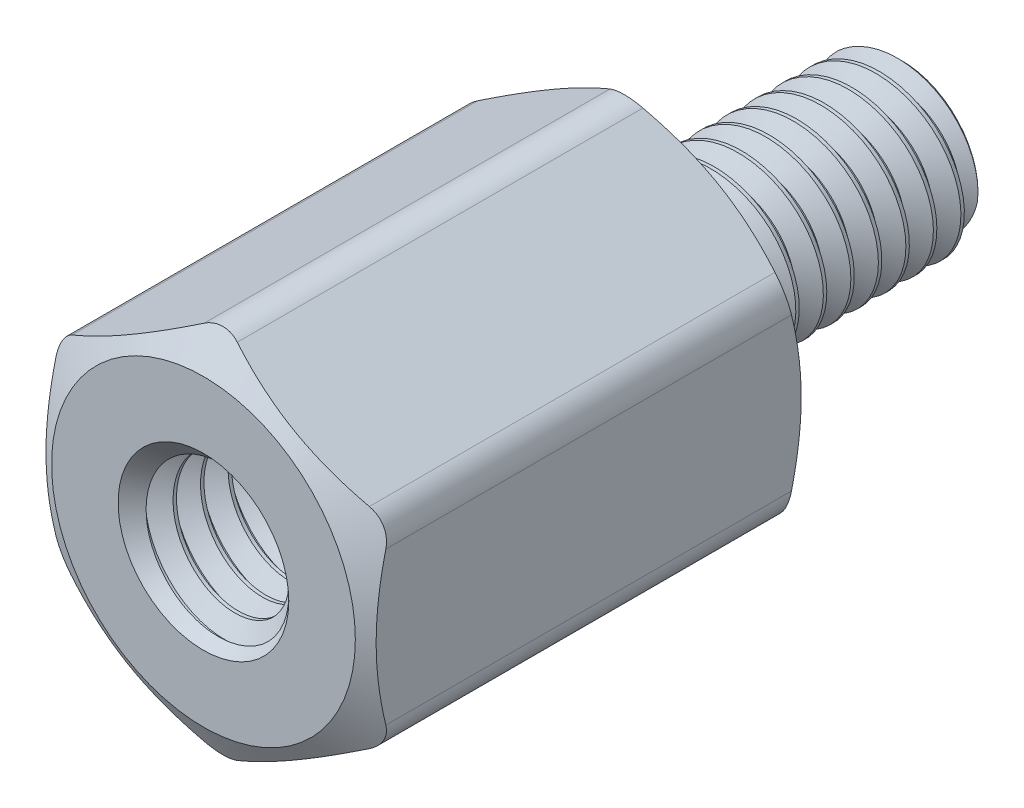
SolidWorks part; units mm, degrees
material "Nylon 6/10"
ref_plane "Front Plane" through (0, 0, 0) normal (0, 0, 1) x (1, 0, 0)
ref_plane "Top Plane" through (0, 0, 0) normal (0, 1, 0) x (1, 0, 0)
ref_plane "Right Plane" through (0, 0, 0) normal (1, 0, 0) x (0, 0, -1)
sketch "Sketch1" plane through (0, 0, 0) normal (0, 0, 1) x (1, 0, 0)
  line L1 (3, 1.7321) -> (0, 3.4641)
  line L2 (0, 3.4641) -> (-3, 1.7321)
  line L3 (-3, 1.7321) -> (-3, -1.7321)
  line L4 (-3, -1.7321) -> (0, -3.4641)
  line L5 (0, -3.4641) -> (3, -1.7321)
  line L6 (3, -1.7321) -> (3, 1.7321)
  circle A0 centre (0, 0) radius 3 construction
  point P10 (0, -3)
  dimension "Hex Size" = 6
sketch "Sketch2" plane through (0, 0, 0) normal (1, 0, 0) x (0, 0, -1)
  line L0 (4.7, 0) -> (-8, 0) construction
  line L2 (0, 1.5) -> (0, -1.5) construction
  line L3 (-3.2, 1.5) -> (-3.2, -1.5) construction
  line L4 (-8.4688, 1.5541) -> (-8.2188, 1.1211) construction
  line L5 (-8.2188, 1.1211) -> (-7.9688, 1.5541) construction
  line L6 (-7.9688, 1.5541) -> (-8.4688, 1.5541) construction
  line L7 (-8.4375, 1.5) -> (-8, 1.5) construction
  line L8 (-8.25, 1.1752) -> (-8.1875, 1.1752) construction
  line L9 (-8.2188, 1.1752) -> (-8.2188, 1.1211) construction
  line L10 (-8.2188, 1.5) -> (-8.2188, 1.5541) construction
  line L11 (4.6688, 1.5541) -> (5.1688, 1.5541) construction
  line L12 (5.1688, 1.5541) -> (4.9188, 1.1211) construction
  line L13 (4.9188, 1.1211) -> (4.6688, 1.5541) construction
  line L14 (4.7, 1.5) -> (5.1375, 1.5) construction
  line L15 (4.8875, 1.1752) -> (4.95, 1.1752) construction
  line L16 (4.9188, 1.1752) -> (4.9188, 1.1211) construction
  line L17 (4.9188, 1.5) -> (4.9188, 1.5541) construction
  line L18 (0, 3.4641) -> (-8, 3.4641) construction
  point P6 (0, 0)
  point P9 (-3.2, 0)
  dimension "Length" = 8
sketch "Sketch3" plane through (0, 0, 0) normal (1, 0, 0) x (0, 0, -1)
  line L0 (-3.2, 0) -> (4.7, 0)
  line L1 (-3.2, 1.5) -> (-3.2, -1.5) construction
  line L2 (4.7, 0) -> (4.7, 1.375)
  line L3 (4.7, 1.375) -> (4.575, 1.5)
  line L4 (4.575, 1.5) -> (0.7515, 1.5)
  line L5 (0.7515, 1.5) -> (0.564, 1.1752)
  line L6 (-3.2, 0) -> (-3.2, 1.375)
  line L7 (-3.2, 1.375) -> (-3.325, 1.5)
  line L8 (-3.325, 1.5) -> (-7.875, 1.5)
  line L9 (-7.875, 1.5) -> (-8, 1.625)
  line L10 (4.575, 0) -> (4.575, -1.5) construction
  line L11 (-8, 1.625) -> (-8, 3)
  line L12 (-8, 3) -> (0, 3)
  line L14 (0.564, 1.1752) -> (0.125, 1.1752)
  line L15 (0, 1.3002) -> (0, 3)
  arc A0 (0, 1.3002) -> (0.125, 1.1752) centre (0.125, 1.3002) ccw
  point P5 (-8, -3)
  point P8 (-6.75, -1.5)
  point P9 (3.45, -1.5)
  point P27 (0, 1.1752)
  dimension "D4" = 0.125
  dimension "D2" = 0.125
  dimension "D1" = 45
  dimension "D6" = 1.25
  dimension "D7" = 60
  dimension "D3" = 1.25
  dimension "D5" = 0.564
revolve "Revolve1" add sketch "Sketch3" angle 360 about L0 region at (0, 1.5061, 1.658)
sketch "Sketch4" plane through (0, 0, 8) normal (0, 0, 1) x (1, 0, 0)
  line L0 (0, 3) -> (0, 1.5) construction
  line L1 (-3, 1.7321) -> (-3, -1.7321)
  line L2 (-3, -1.7321) -> (0, -3.4641)
  line L3 (0, -3.4641) -> (3, -1.7321)
  line L4 (3, -1.7321) -> (3, 1.7321)
  line L5 (3, 1.7321) -> (0, 3.4641)
  line L6 (0, 3.4641) -> (-3, 1.7321)
  circle A0 centre (0, 0) radius 3 construction
  circle A1 centre (0, 0) radius 2.25
  circle A2 centre (0, 0) radius 3 construction
  point P16 (0, 2.25)
extrude "Boss-Extrude1" add sketch "Sketch4" against normal up to surface (8 mm away) up to face at (0, 3, 0)
sketch "Sketch5" plane through (0, 0, 8) normal (0, 0, 1) x (1, 0, 0)
  line L0 (-0.8604, 1.2287) -> (0.8604, -1.2287) construction
  line L1 (0, 1.5) -> (0, -1.5) construction
  line L3 (0, -3.7084) -> (0, 3.7084) construction
  circle A0 centre (0, 0) radius 2.76
  point P11 (0.8604, -1.2287)
  dimension "D1" = 5.52
  dimension "D2" = 35
extrude "Cut-Extrude1" cut sketch "Sketch5" against normal through all draft 60 flip side to cut
sketch "Sketch6" plane through (0, 0, 0) normal (0, 0, -1) x (-1, 0, 0)
  circle A0 centre (0, 0) radius 2.76
  circle A1 centre (0, 0) radius 2.76 construction
extrude "Cut-Extrude2" cut sketch "Sketch6" against normal through all draft 60 flip side to cut
fillet "Fillet1" radius 0.6 6 edges at (0, 3.4641, 4) (-3, -1.7321, 4) (0, -3.4641, 4) (3, -1.7321, 4) (3, 1.7321, 4) (-3, 1.7321, 4)
sketch "Drawing1" plane through (0, 0, 0) normal (1, 0, 0) x (0, 0, -1)
  line L0 (-8, 1.5) -> (-3.2, 1.5) construction
  line L1 (-3.2, 1.5) -> (-3.2, -1.5) construction
  line L2 (-3.2, -1.5) -> (-8, -1.5) construction
sketch "Sketch7" plane through (0, 0, 0) normal (-1, 0, 0) x (0, 0, 1)
  line L0 (-4.8875, 1.1752) -> (-4.95, 1.1752)
  line L1 (-4.95, 1.1752) -> (-5.1531, 1.5271)
  line L2 (-5.1688, 1.5541) -> (-4.9188, 1.1211) construction
  line L3 (-5.1531, 1.5271) -> (-4.6844, 1.5271)
  line L4 (-4.9188, 1.1211) -> (-4.6688, 1.5541) construction
  line L5 (-4.6844, 1.5271) -> (-4.8875, 1.1752)
  line L6 (-4.9188, 1.5) -> (-4.9188, 1.5541) construction
  point P12 (-4.9188, 1.5271)
sketch "Sketch8" plane through (0, 0, -4.7) normal (0, 0, -1) x (-1, 0, 0)
  circle A0 centre (0, 0) radius 1.5
curve "Helix/Spiral1" pitch 0.5 height 4.559 radius 1.5 centre (0, 0, -4.7) axis (0, 0, 1) start towards (0, 1, 0)
sweep "Cut-Sweep1" cut profiles "Sketch7" path "Helix/Spiral1" align with end faces yes
sketch "Sketch9" plane through (0, 0, 3.2) normal (0, 0, 1) x (1, 0, 0)
  circle A0 centre (0, 0) radius 1.625
extrude "Boss-Extrude2" add sketch "Sketch9" along normal up to surface (4.8 mm away) up to face at (0, 1.625, 8)
sketch "Sketch10" plane through (0, 0, 0) normal (1, 0, 0) x (0, 0, -1)
  line L0 (4.7, 0) -> (-8, 0) construction
  line L1 (-3.2, 1.5) -> (-8, 1.5)
  line L2 (-3.2, 1.5) -> (-3.2, 0)
  line L3 (-3.2, 0) -> (-8, 0)
  line L4 (-8, 1.5) -> (-8, 0)
revolve "Revolve2" add sketch "Sketch10" angle 360 about L0
sketch "Sketch11" plane through (0, 0, 8) normal (0, 0, 1) x (1, 0, 0)
  circle A0 centre (0, 0) radius 1.5
  circle A1 centre (0, 0) radius 1.5 construction
sketch "Sketch12" plane through (0, 0, 0) normal (1, 0, 0) x (0, 0, -1)
  line L0 (-8.25, 1.1752) -> (-8.1875, 1.1752)
  line L1 (-8.1875, 1.1752) -> (-7.9844, 1.5271)
  line L2 (-8.2188, 1.1211) -> (-7.9688, 1.5541) construction
  line L3 (-7.9844, 1.5271) -> (-8.4531, 1.5271)
  line L4 (-8.4688, 1.5541) -> (-8.2188, 1.1211) construction
  line L5 (-8.4531, 1.5271) -> (-8.25, 1.1752)
  line L6 (-8.2188, 1.5) -> (-8.2188, 1.5541) construction
  point P12 (-8.2188, 1.5271)
curve "Helix/Spiral2" pitch 0.5 height 5.3 radius 1.5 centre (0, 0, 8) axis (0, 0, -1) start towards (0, 1, 0)
sweep "Cut-Sweep2" cut profiles "Sketch12" path "Helix/Spiral2" align with end faces yes
combine bodies "Combine1" operation type subtract main body 113 bodies to subtract 114
sketch "Sketch13" plane through (0, 0, 8) normal (0, 0, 1) x (1, 0, 0)
  circle A0 centre (0, 0) radius 1.5508
  dimension "D1" = 0.0508
extrude "Cut-Extrude3" cut sketch "Sketch13" against normal through all draft 45
equation "\"Thread Pitch (B)/8@Sketch2\" = \"Thread Pitch (B)@Sketch2\" / 8"
equation "\"Thread Pitch (A)/8@Sketch2\" = \"Thread Pitch (A)@Sketch2\" / 8"
equation "\"D1@Sketch5\"=\"Hex Size@Sketch1\" * .92"
equation "\"D1@Fillet1\" = \"Hex Size@Sketch1\" * .1"
equation "\"D2@Sketch3\" = \"Thread Pitch (A)@Sketch2\" * .25"
equation "\"D4@Sketch3\" = \"D2@Sketch3\""
equation "\"D6@Sketch3\" = \"Thread Pitch (A)@Sketch2\" * 2.5"
equation "\"D3@Helix/Spiral1\" = \"Thread Length (A)@Sketch2\" - \"D5@Sketch3\" * .25"
equation "\"D4@Helix/Spiral1\" = \"Thread Pitch (A)@Sketch2\""
equation "\"D3@Sketch3\" = \"Thread Pitch (B)@Sketch2\" * 2.5"
equation "\"D5@Sketch3\" = \"Thread Length (A)@Sketch2\" * .12"
equation "\"D3@Helix/Spiral2\" = \"Minimum Thread Length (B)@Sketch2\" + \"Thread Pitch (B)@Sketch2\""
equation "\"D4@Helix/Spiral2\" = \"Thread Pitch (B)@Sketch2\""
